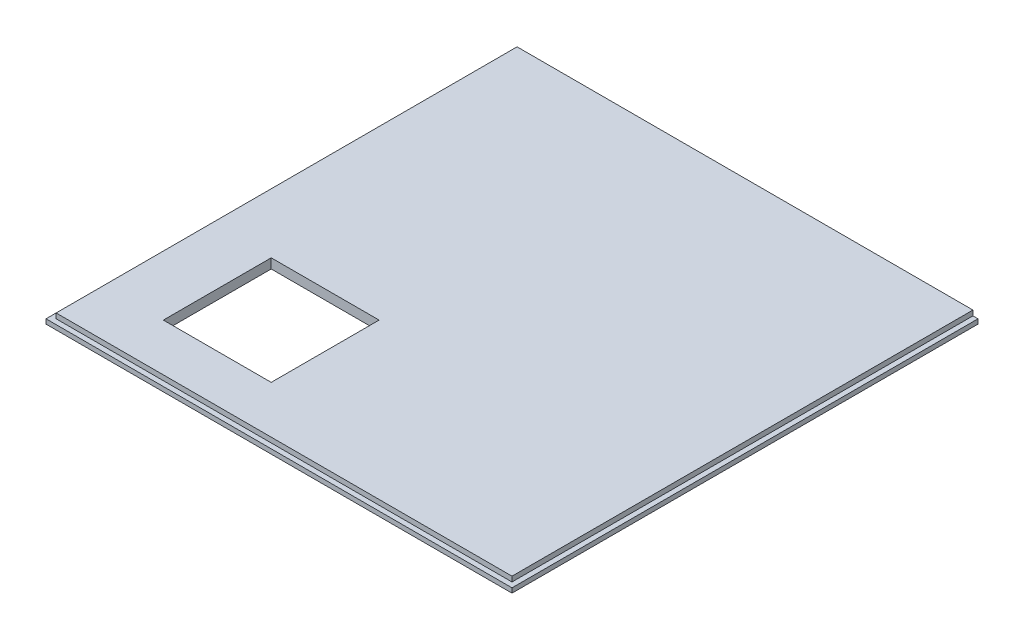
SolidWorks part; units mm, degrees
ref_plane "Front Plane" through (0, 0, 0) normal (0, 0, 1) x (1, 0, 0)
ref_plane "Top Plane" through (0, 0, 0) normal (0, 1, 0) x (1, 0, 0)
ref_plane "Right Plane" through (0, 0, 0) normal (1, 0, 0) x (0, 0, -1)
sketch "Sketch1" plane through (0, 0, 0) normal (0, 1, 0) x (1, 0, 0)
  line L1 (-438.9437, -438.9437) -> (438.9438, -438.9437)
  line L2 (-438.9437, -438.9437) -> (-438.9437, 438.9438)
  line L3 (-438.9437, 438.9438) -> (438.9438, 438.9438)
  line L4 (438.9438, -438.9437) -> (438.9438, 438.9438)
  line L5 (-438.9437, -438.9437) -> (438.9438, 438.9438) construction
  line L6 (-438.9437, 438.9438) -> (438.9438, -438.9437) construction
  point P0 (0, 0)
  dimension "D1" = 877.8875
  dimension "D2" = 877.8875
extrude "Boss-Extrude1" add sketch "Sketch1" along normal blind 18.2562 contours L2 L1 L4 L3
sketch "Sketch3" plane through (0, 18.2562, 0) normal (0, 1, 0) x (1, 0, 0)
  line L3 (429.4188, 438.9438) -> (438.9437, 438.9437)
  line L5 (438.9437, 438.9437) -> (438.9437, -438.9437)
  line L6 (429.4188, -429.4187) -> (429.4188, 438.9438)
  line L7 (-429.4187, -429.4187) -> (429.4188, -429.4187)
  line L8 (-429.4187, 438.9438) -> (-429.4187, -429.4187)
  line L9 (429.4188, -429.4187) -> (429.4188, 438.9438)
  line L10 (-429.4187, -429.4187) -> (429.4188, -429.4187)
  line L11 (-429.4187, 438.9438) -> (-429.4187, -429.4187)
  line L12 (438.9437, -438.9437) -> (-438.9437, -438.9437)
  line L13 (-438.9437, 438.9437) -> (-438.9437, -438.9437)
  line L14 (438.9437, 438.9437) -> (-438.9437, -438.9437) construction
  line L15 (438.9437, -438.9437) -> (-438.9437, 438.9437) construction
  line L16 (-429.4187, 438.9438) -> (-438.9437, 438.9437)
  point P0 (0, 0)
  dimension "D1" = 9.525
extrude "Cut-Extrude1" cut sketch "Sketch3" against normal blind 9.525
sketch "Sketch4" plane through (0, 18.2562, 0) normal (0, 1, 0) x (1, 0, 0)
  line L1 (-316.7512, -136.8418) -> (-113.5512, -136.8418)
  line L2 (-316.7512, -136.8418) -> (-316.7512, -340.0418)
  line L3 (-316.7512, -340.0418) -> (-113.5512, -340.0418)
  line L4 (-113.5512, -136.8418) -> (-113.5512, -340.0418)
extrude "Cut-Extrude2" cut sketch "Sketch4" against normal blind 19.05 contours L2 L1 L4 L3
